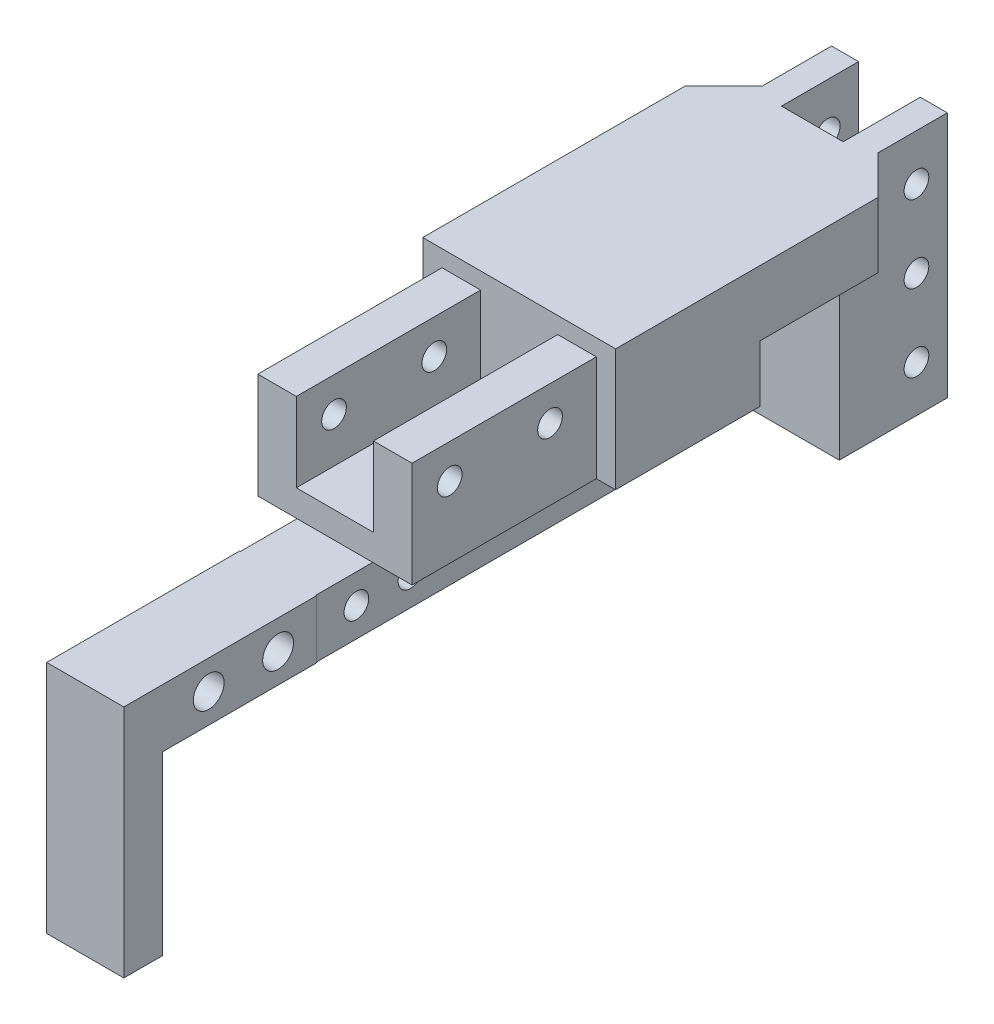
SolidWorks part; units mm, degrees
ref_plane "前视基准面" through (0, 0, 0) normal (0, 0, 1) x (1, 0, 0)
ref_plane "上视基准面" through (0, 0, 0) normal (0, 1, 0) x (1, 0, 0)
ref_plane "右视基准面" through (0, 0, 0) normal (1, 0, 0) x (0, 0, -1)
sketch "草图2" plane through (0, 0, 0) normal (1, 0, 0) x (0, 0, -1)
  line L0 (7, 0) -> (32.5, 0) construction
  line L2 (44.75, 3.775) -> (-5.25, 3.775)
  line L3 (44.75, 3.775) -> (44.75, -3.775)
  line L4 (44.75, -3.775) -> (-5.25, -3.775)
  line L5 (-5.25, 3.775) -> (-5.25, -3.775)
  line L6 (44.75, 3.775) -> (-5.25, -3.775) construction
  line L7 (44.75, -3.775) -> (-5.25, 3.775) construction
  circle A0 centre (0, 0) radius 1.6
  circle A1 centre (7, 0) radius 1.6
  circle A2 centre (32.5, 0) radius 1.6
  circle A3 centre (39.5, 0) radius 1.6
  point P9 (19.75, 0)
  dimension "D1" = 25.5
  dimension "D2" = 7
  dimension "D3" = 3.775
extrude "凸台-拉伸1" add sketch "草图2" along normal mid plane 9.8
sketch "草图3" plane through (0, 0, 0) normal (1, 0, 0) x (0, 0, -1)
  line L0 (7, 13) -> (20, 13) construction
  line L1 (2.1144, 3.775) -> (2.1144, 17.4551)
  line L2 (44.75, 3.775) -> (-5.25, 3.775) construction
  line L3 (2.1144, 17.4551) -> (26, 17.4551)
  line L4 (26, 17.4551) -> (26, 3.775)
  line L5 (26, 3.775) -> (2.1144, 3.775)
  circle A0 centre (7, 13) radius 1.6
  circle A1 centre (20, 13) radius 1.6
  point P0 (7, 0)
  point P6 (13.5, 13)
  dimension "D1" = 13
  dimension "D3" = 3.2
  dimension "D4" = 3.2
  dimension "D2" = 6
extrude "凸台-拉伸2" add sketch "草图3" along normal mid plane 20
sketch "草图4" plane through (0, 0, -2.1144) normal (0, 0, 1) x (1, 0, 0)
  line L0 (10, 17.4551) -> (-10, 17.4551) construction
  line L1 (5, 7.1905) -> (-5, 7.1905)
  line L2 (5, 7.1905) -> (5, 17.4551)
  line L3 (5, 17.4551) -> (-5, 17.4551)
  line L4 (-5, 7.1905) -> (-5, 17.4551)
  line L5 (5, 7.1905) -> (-5, 17.4551) construction
  line L6 (5, 17.4551) -> (-5, 7.1905) construction
  point P0 (0, 12.3228)
extrude "切除-拉伸1" cut sketch "草图4" against normal through all
sketch "草图6" plane through (0, 0, 0) normal (1, 0, 0) x (0, 0, -1)
  line L0 (70, 3.6) -> (70, 13.6) construction
  line L2 (74, -12.4) -> (60, -12.4)
  line L3 (74, -12.4) -> (74, 19.6)
  line L4 (74, 19.6) -> (60, 19.6)
  line L5 (60, -12.4) -> (60, 19.6)
  line L6 (74, -12.4) -> (60, 19.6) construction
  line L7 (74, 19.6) -> (60, -12.4) construction
  circle A0 centre (70, 3.6) radius 1.6
  circle A1 centre (70, 13.6) radius 1.6
  circle A2 centre (70, -6.4) radius 1.6
  point P4 (70, 8.6)
  point P9 (67, 3.6)
  dimension "D1" = 60
  dimension "D6" = 10
  dimension "D2" = 3.6
  dimension "D3" = 10
  dimension "D4" = 4
  dimension "D5" = 14
  dimension "D7" = 6
  dimension "D8" = 6
extrude "凸台-拉伸4" add sketch "草图6" along normal mid plane 15 separate body
sketch "草图7" plane through (0, 0, -74) normal (0, 0, 1) x (1, 0, 0)
  line L0 (7.5, 19.6) -> (-7.5, 19.6) construction
  line L1 (-4, 19.6) -> (4, 19.6)
  line L2 (-4, 19.6) -> (-4, -12.4)
  line L3 (-4, -12.4) -> (4, -12.4)
  line L4 (4, 19.6) -> (4, -12.4)
  line L5 (7.5, -12.4) -> (-7.5, -12.4) construction
extrude "切除-拉伸2" cut sketch "草图7" along normal blind 10
sketch "草图8" plane through (0, 0, 0) normal (1, 0, 0) x (0, 0, -1)
  line L0 (26, 3.775) -> (26, 17.4551) construction
  line L1 (60, 19.6) -> (26, 19.6)
  line L2 (60, 19.6) -> (60, 11.1399)
  line L3 (60, 11.1399) -> (44.75, 11.1399)
  line L4 (26, 19.6) -> (26, 11.1399)
  line L7 (26, 11.1399) -> (26, 3.775)
  line L8 (26, 3.775) -> (44.75, 3.775)
  line L9 (44.75, 11.1399) -> (44.75, 3.775)
extrude "凸台-拉伸5" add sketch "草图8" along normal mid plane 25
chamfer "倒角1" distance 5 angle 45 2 edges at (-7.5, 15.37, -60) (7.5, 15.37, -60)
sketch "草图10" plane through (0, 0, 0) normal (1, 0, 0) x (0, 0, -1)
  line L0 (-5.25, 3.775) -> (-5.25, -3.775)
  line L1 (-5.25, -3.775) -> (-25.25, -3.775)
  line L2 (-25.25, -3.775) -> (-25.25, -26.6539)
  line L3 (-30.25, -26.6539) -> (-30.25, 3.775)
  line L4 (-30.25, 3.775) -> (-5.25, 3.775)
  line L5 (-30.25, -26.6539) -> (-25.25, -26.6539)
  circle A0 centre (-10.25, 0) radius 2
  circle A1 centre (-19.25, 0) radius 2
  dimension "D3" = 4
  dimension "D4" = 4
  dimension "D1" = 20
  dimension "D2" = 5
  dimension "D5" = 9
  dimension "D6" = 5
extrude "凸台-拉伸6" add sketch "草图10" along normal mid plane 10
